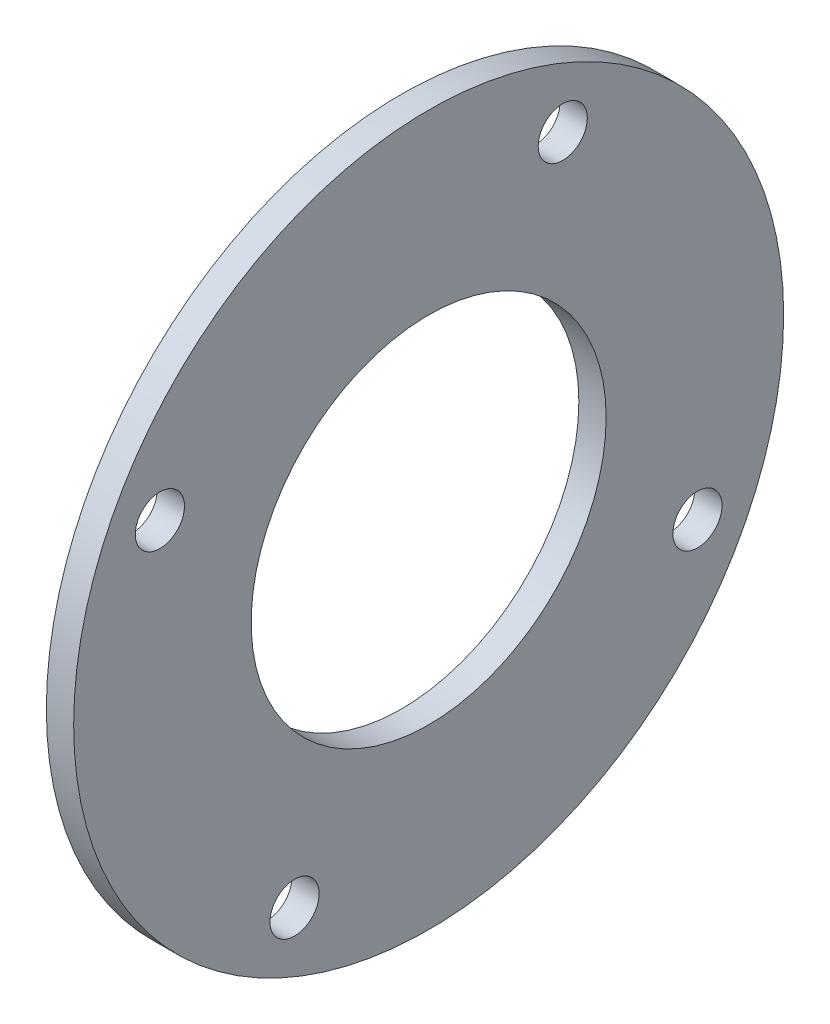
SolidWorks part; units mm, degrees
ref_plane "Спереди" through (0, 0, 0) normal (0, 0, 1) x (1, 0, 0)
ref_plane "Сверху" through (0, 0, 0) normal (0, 1, 0) x (1, 0, 0)
ref_plane "Справа" through (0, 0, 0) normal (1, 0, 0) x (0, 0, -1)
sketch "Эскиз1" plane through (0, 0, 0) normal (1, 0, 0) x (0, 0, -1)
  circle A0 centre (0, 0) radius 26
  circle A1 centre (0, 0) radius 13
  circle A2 centre (0, 0) radius 13 construction
  circle A3 centre (0, 0) radius 26 construction
extrude "Бобышка-Вытянуть1" add sketch "Эскиз1" along normal blind 2
hole_wizard "Зенковка для винта с полупотайной головкой M32" positions "Эскиз6" profile "Эскиз7" hole size "M3" standard "DIN" end condition up to next
sketch "Эскиз6" plane through (0, 0, 0) normal (-1, 0, 0) x (0, 0, 1)
  circle A0 centre (19.686, 9.8215) radius 1.8 construction
  point P0 (19.686, 9.8215)
sketch "Эскиз7" plane through (0, 9.8215, 19.686) normal (0, 1, 0) x (0, 0, 1)
  line L0 (0, 0) -> (0, 2)
  line L1 (0, 2) -> (1.8, 2)
  line L2 (1.8, 2) -> (1.8, 0)
  line L5 (1.8, 0) -> (0, 0)
  line L11 (0, -6.35) -> (0, 107.95) construction
  dimension "Диаметр сквозного отверстия" = 3.6
  dimension "Глубина сквозного отверстия" = 2
pattern_circular "Круговой массив1" count 4 over 360 about axis through (0, 0, 0) along (1, 0, 0) of "Зенковка для винта с полупотайной головкой M32"
